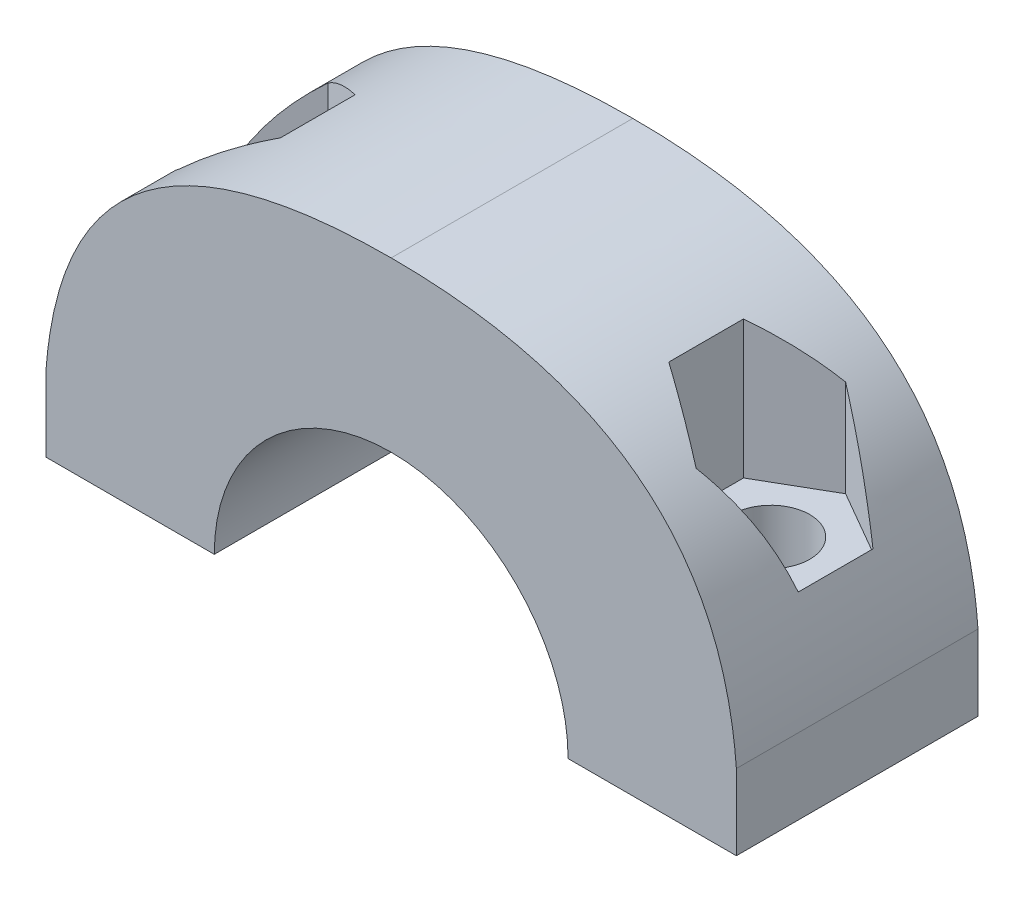
SolidWorks part; units mm, degrees
ref_plane "Front Plane" through (0, 0, 0) normal (0, 0, 1) x (1, 0, 0)
ref_plane "Top Plane" through (0, 0, 0) normal (0, 1, 0) x (1, 0, 0)
ref_plane "Right Plane" through (0, 0, 0) normal (1, 0, 0) x (0, 0, -1)
sketch "Sketch1" plane through (0, 0, 0) normal (0, 0, 1) x (1, 0, 0)
  line L0 (10.25, 0) -> (20, 0)
  line L1 (-20, 0) -> (-10.25, 0)
  line L2 (-20, 0) -> (-20, 20)
  line L3 (-20, 20) -> (20, 20)
  line L4 (20, 0) -> (20, 20)
  arc A3 (10.25, 0) -> (-10.25, 0) centre (0, 0) ccw
  point P4 (0, 20)
  point P5 (6.375, -10.25)
  point P9 (0, 0)
  point P10 (-6.375, -10.5966)
  dimension "D1" = 20.5
  dimension "D6" = 40
  dimension "D2" = 20
extrude "Boss-Extrude1" add sketch "Sketch1" along normal mid plane 14
sketch "Sketch2" plane through (0, 0, 7) normal (0, 0, 1) x (1, 0, 0)
  line L0 (0, 20) -> (0, 0)
  line L1 (20, 20) -> (-20, 20) construction
fillet "Fillet1" radius 2 2 edges at (20, 0, 0) (-20, 0, 0)
split "Split1" trim tools "Sketch2" bodies to split 101 resulting bodies 102 103
sketch "Sketch6" plane through (0, 0, 7) normal (0, 0, 1) x (1, 0, 0)
  line L0 (-20, 20) -> (-20, 2) construction
  line L1 (0, 20) -> (-20, 20) construction
  line L2 (-20, 20) -> (-20, -0.0764)
  line L3 (20, 20) -> (-20, 20)
  line L4 (0, 0) -> (0, 3.3922) construction
  line L5 (0, 20) -> (0, 10.25) construction
  line L6 (20, 20) -> (20, -0.0764)
  line L8 (0, 20) -> (0, 10.25) construction
  spline S0 degree 2 poles (0, 20) (-21.3365, 20) (-20, -0.0764) knots 0 0 0 1 1 1
  spline S1 degree 2 poles (0, 20) (21.3365, 20) (20, -0.0764) knots 0 0 0 1 1 1
  point P0 (0, 19.75)
  point P13 (0, 19.75)
  line M2 (0, 20) -> (-20, 20)
  line M3 (-20, 20) -> (-20, 2)
extrude "Cut-Extrude2" cut sketch "Sketch6" against normal up to next (14 mm away) contours S0 M2 M3 region at (-15.9751, 16.5462, 7)
extrude "Cut-Extrude8" cut sketch "Sketch6<3>" against normal through all contours L3 S1 L6 region at (15.9751, 16.5462, 7)
sketch "Sketch6<3>" plane through (0, 0, 7) normal (0, 0, 1) x (1, 0, 0) same geometry as "Sketch6"
sketch "Sketch10" plane through (0, 0, 0) normal (0, -1, 0) x (1, 0, 0)
  line L0 (0, 0) -> (0, 2.25) construction
  line L2 (0, -7) -> (0, 7) construction
  line L3 (18, -7) -> (18, 7) construction
  circle A2 centre (15, 0) radius 2.25
  circle A3 centre (-15, 0) radius 2.25
  point P11 (18, 0)
  point P12 (15.3022, 0)
  dimension "D1" = 4.5
  dimension "D2" = 30
extrude "Cut-Extrude6" cut sketch "Sketch10" against normal blind 35
ref_plane "Plane1" through (0, 20, 0) normal (0, 1, 0) x (1, 0, 0)
sketch "Sketch11" plane through (0, 20, 0) normal (0, 1, 0) x (1, 0, 0)
  line L0 (0, -7) -> (0, 7) construction
  line L1 (-11.25, -2.1651) -> (-11.25, 2.1651)
  line L2 (-11.25, 2.1651) -> (-15, 4.3301)
  line L3 (-15, 4.3301) -> (-18.75, 2.1651)
  line L4 (-18.75, 2.1651) -> (-18.75, -2.1651)
  line L5 (-18.75, -2.1651) -> (-15, -4.3301)
  line L6 (-15, -4.3301) -> (-11.25, -2.1651)
  line L7 (15, -4.3301) -> (11.25, -2.1651)
  line L8 (18.75, -2.1651) -> (15, -4.3301)
  line L9 (18.75, 2.1651) -> (18.75, -2.1651)
  line L10 (15, 4.3301) -> (18.75, 2.1651)
  line L11 (11.25, 2.1651) -> (15, 4.3301)
  line L12 (11.25, -2.1651) -> (11.25, 2.1651)
  circle A0 centre (-15, 0) radius 3.75 construction
  circle A1 centre (15, 0) radius 3.75 construction
  point P1 (0, 0)
  point P10 (-11.25, 0)
  point P11 (0, 0)
  point P22 (-14.5, 0)
  point P23 (-10.6538, 0.8439)
  point P24 (-17, 0)
  dimension "D1" = 7.5
extrude "Cut-Extrude7" cut sketch "Sketch11" against normal blind 10
combine bodies "Combine1" operation type add bodies to combine 112 119
sketch "Sketch12" plane through (0, 0, 7) normal (0, 0, 1) x (1, 0, 0)
  line L0 (-18, 0) -> (-20, 0)
  line L1 (-20, 0) -> (-20, 2)
  line L3 (0, 0) -> (0, 2.5514) construction
  line L4 (18, 0) -> (20, 0)
  line L5 (20, 0) -> (20, 2)
  arc A0 (-20, 2) -> (-18, 0) centre (-18, 2) ccw construction
  arc A1 (-20, 2) -> (-18, 0) centre (-18, 2) ccw
  arc A2 (18, 0) -> (20, 2) centre (18, 2) ccw construction
  arc A3 (18, 0) -> (20, 2) centre (18, 2) ccw
extrude "Boss-Extrude2" add sketch "Sketch12" against normal up to surface (14 mm away) up to face at (-2.2222, 4.6864, -7)
